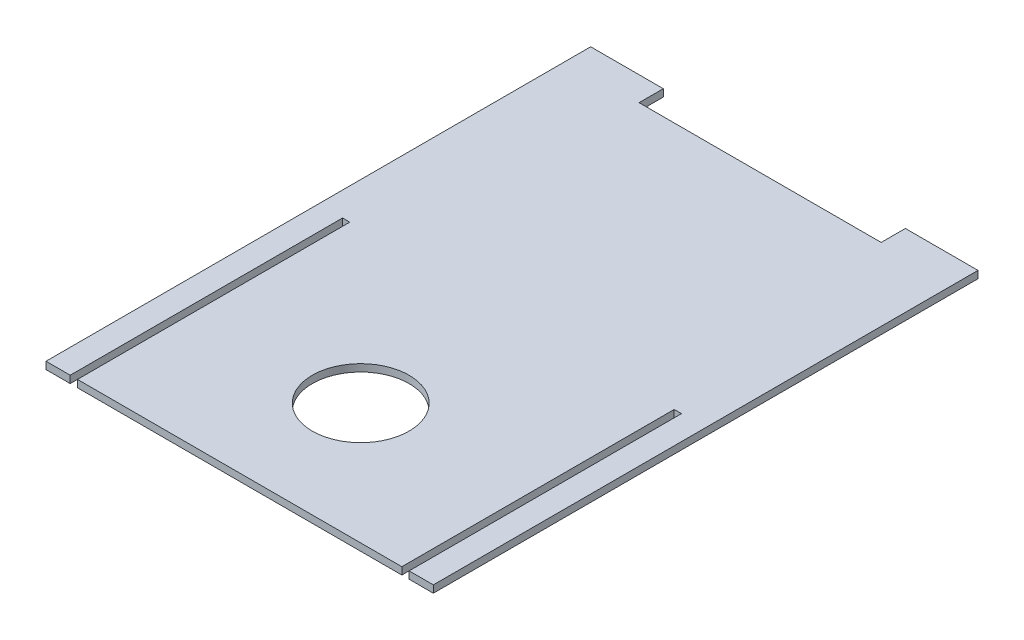
SolidWorks part; units mm, degrees
ref_plane "Front Plane" through (0, 0, 0) normal (0, 0, 1) x (1, 0, 0)
ref_plane "Top Plane" through (0, 0, 0) normal (0, 1, 0) x (1, 0, 0)
ref_plane "Right Plane" through (0, 0, 0) normal (1, 0, 0) x (0, 0, -1)
sketch "Sketch1" plane through (0, 0, 0) normal (0, 1, 0) x (1, 0, 0)
  line L1 (0, 0) -> (320, 0)
  line L2 (0, 0) -> (0, 450)
  line L3 (0, 450) -> (320, 450)
  line L4 (320, 0) -> (320, 450)
  dimension "D1" = 320
  dimension "D2" = 450
extrude "Boss-Extrude1" add sketch "Sketch1" along normal blind 6
sketch "Sketch2" plane through (0, 6, 0) normal (0, 1, 0) x (1, 0, 0)
  line L0 (0, 0) -> (320, 0) construction
  line L1 (20, 0) -> (26, 0)
  line L2 (20, 0) -> (20, 225)
  line L3 (20, 225) -> (26, 225)
  line L4 (26, 0) -> (26, 225)
  line L5 (0, 450) -> (0, 0) construction
  dimension "D1" = 225
  dimension "D2" = 6
  dimension "D3" = 20
extrude "Cut-Extrude1" cut sketch "Sketch2" against normal blind 6
pattern_linear "LPattern1" count 2 spacing 274 along (1, 0, 0) of "Cut-Extrude1"
sketch "Sketch3" plane through (0, 6, 0) normal (0, 1, 0) x (1, 0, 0)
  line L1 (320, 0) -> (320, 450) construction
  line L2 (26, 0) -> (294, 0) construction
  line L3 (320, 450) -> (0, 450) construction
  line L4 (60, 450) -> (260, 450)
  line L5 (60, 450) -> (60, 430)
  line L6 (60, 430) -> (260, 430)
  line L7 (260, 450) -> (260, 430)
  line L8 (0, 450) -> (0, 0) construction
  circle A0 centre (160, 100) radius 40
  point P14 (160, 450)
  dimension "D1" = 160
  dimension "D2" = 100
  dimension "D3" = 80
  dimension "D4" = 200
  dimension "D5" = 20
  dimension "D6" = 160
extrude "Cut-Extrude2" cut sketch "Sketch3" against normal blind 6
